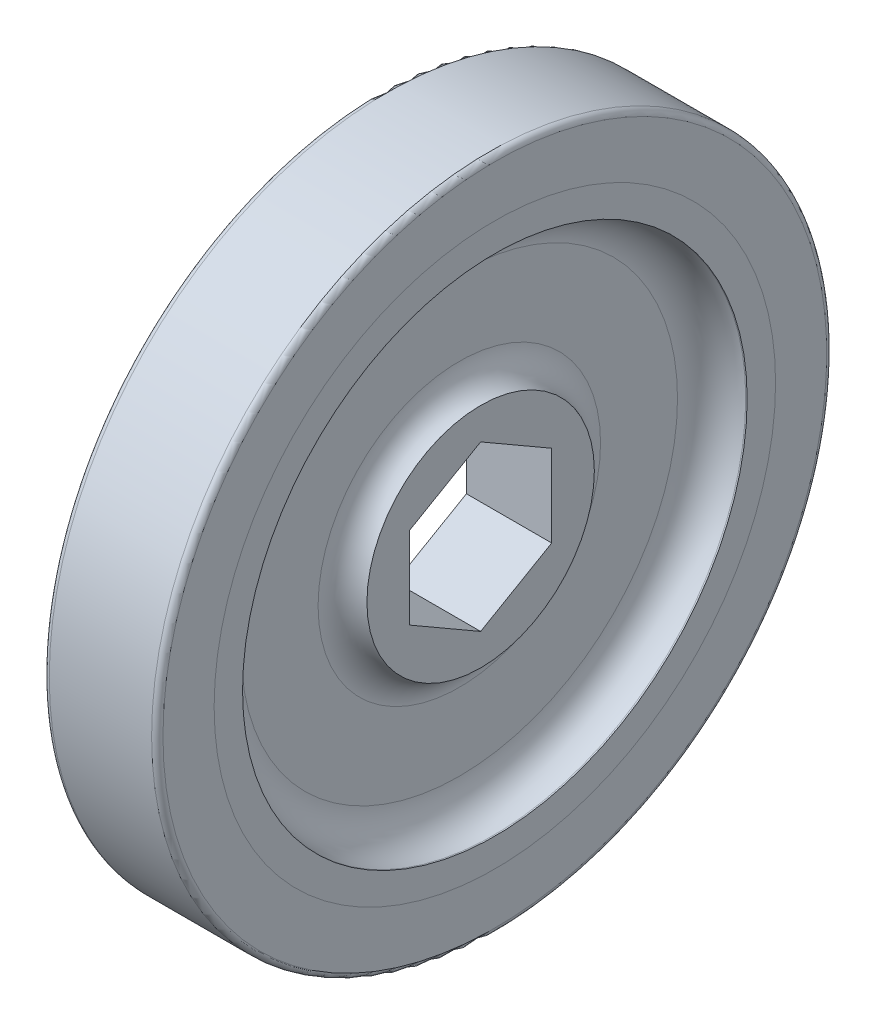
SolidWorks part; units mm, degrees
material "ABS"
ref_plane "Plan de face" through (0, 0, 0) normal (0, 0, 1) x (1, 0, 0)
ref_plane "Plan de dessus" through (0, 0, 0) normal (0, 1, 0) x (1, 0, 0)
ref_plane "Plan de droite" through (0, 0, 0) normal (1, 0, 0) x (0, 0, -1)
sketch "Esquisse1" plane through (0, 0, 0) normal (0, 0, 1) x (1, 0, 0)
  line L0 (0, 0) -> (0, 10.16) construction
  line L1 (1.905, 10.16) -> (3.81, 10.16)
  line L2 (-3.81, 10.16) -> (-3.81, 0)
  line L3 (-3.81, 0) -> (3.81, 0)
  line L4 (3.81, 10.16) -> (3.81, 0)
  line L5 (-1.905, 22.5425) -> (1.905, 22.5425) construction
  line L6 (-1.905, 22.5425) -> (-1.905, 10.16)
  line L7 (-1.905, 10.16) -> (1.905, 10.16) construction
  line L8 (1.905, 22.5425) -> (1.905, 10.16)
  line L9 (-1.905, 10.16) -> (-3.81, 10.16)
  line L10 (-5.08, 22.5425) -> (-1.905, 22.5425)
  line L11 (0, 25.0825) -> (0, 22.5425) construction
  line L12 (-5.08, 25.0825) -> (-5.08, 22.5425)
  line L13 (1.905, 22.5425) -> (5.08, 22.5425)
  line L14 (5.08, 25.0825) -> (5.08, 22.5425)
  line L15 (-2.54, 27.6225) -> (2.54, 27.6225)
  line L16 (-2.54, 27.6225) -> (-2.54, 25.0825)
  line L17 (-2.54, 25.0825) -> (2.54, 25.0825) construction
  line L18 (2.54, 27.6225) -> (2.54, 25.0825)
  line L19 (2.54, 25.0825) -> (5.08, 25.0825)
  line L20 (-2.54, 25.0825) -> (-5.08, 25.0825)
  dimension "D1" = 7.62
  dimension "D2" = 10.16
  dimension "D3" = 3.81
  dimension "D4" = 22.5425
  dimension "D5" = 25.0825
  dimension "D6" = 10.16
  dimension "D7" = 5.08
  dimension "D8" = 27.6225
revolve "Révolution1" add sketch "Esquisse1" angle 360 about L3
fillet "Congé1" radius 2.54 2 edges at (-1.905, 0, 10.16) (1.905, 0, 10.16)
fillet "Congé2" radius 3.048 2 edges at (1.905, 0, 22.5425) (-1.905, 0, 22.5425)
sketch "Esquisse3" plane through (0, 0, 0) normal (1, 0, 0) x (0, 0, -1)
  line L1 (0, 7.3323) -> (-6.35, 3.6662)
  line L2 (-6.35, 3.6662) -> (-6.35, -3.6662)
  line L3 (-6.35, -3.6662) -> (0, -7.3323)
  line L4 (0, -7.3323) -> (6.35, -3.6662)
  line L5 (6.35, -3.6662) -> (6.35, 3.6662)
  line L6 (6.35, 3.6662) -> (0, 7.3323)
  circle A0 centre (0, 0) radius 6.35 construction
  dimension "D1" = 12.7
extrude "hex_hole" cut sketch "Esquisse3" against normal through all and the other way through all
sketch "Esquisse2" plane through (0, 0, 0) normal (0, 0, 1) x (1, 0, 0)
  line L0 (-5.08, 25.0825) -> (-2.54, 25.0825)
  line L1 (-2.54, 25.0825) -> (-2.54, 27.6225)
  line L2 (-2.54, 27.6225) -> (2.54, 27.6225)
  line L3 (2.54, 27.6225) -> (2.54, 25.0825)
  line L4 (2.54, 25.0825) -> (5.08, 25.0825)
  line L5 (5.08, 25.0825) -> (5.08, 30.1625)
  line L6 (5.08, 30.1625) -> (-5.08, 30.1625)
  line L7 (-5.08, 30.1625) -> (-5.08, 25.0825)
  line L8 (-3.81, 0) -> (3.81, 0) construction
  dimension "D1" = 30.1625
revolve "Révolution2" add sketch "Esquisse2" angle 360 about L8
fillet "Congé3" radius 0.508 2 edges at (-5.08, 0, 30.1625) (5.08, 0, 30.1625)
